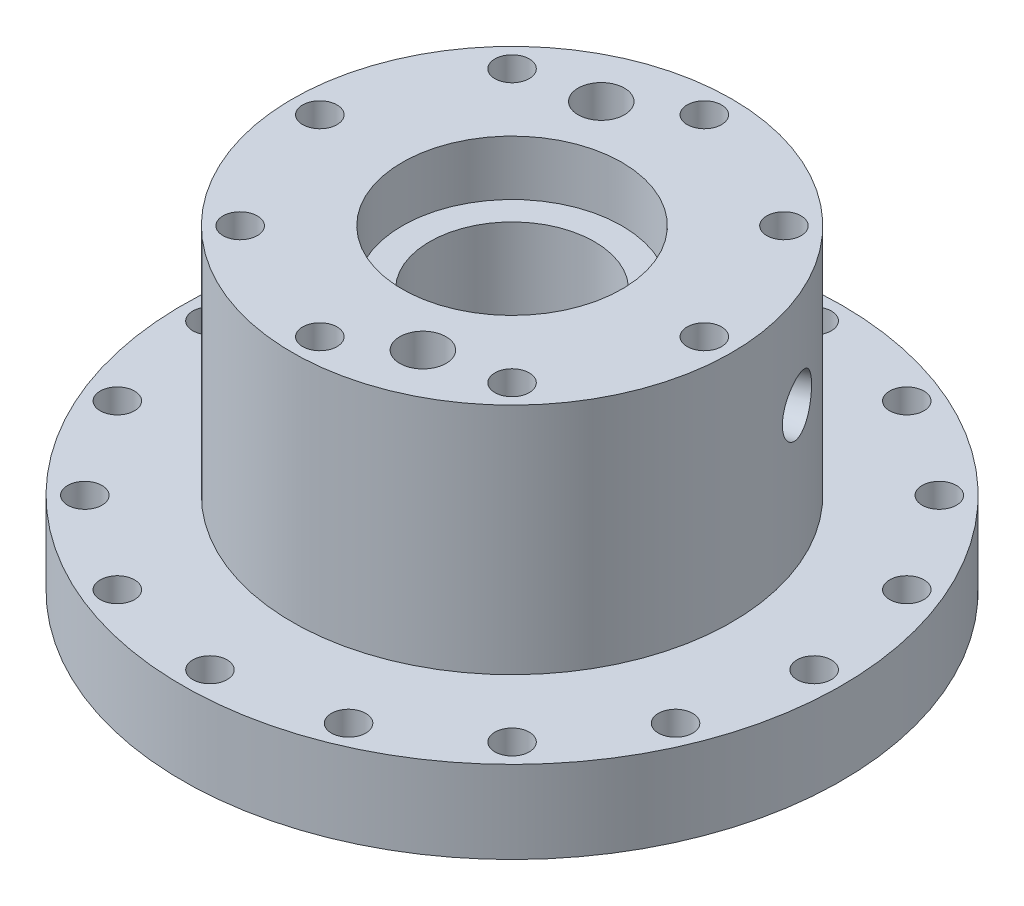
SolidWorks part; units mm, degrees
material "6061-T4 (SS)"
ref_plane "Front Plane" through (0, 0, 0) normal (0, 0, 1) x (1, 0, 0)
ref_plane "Top Plane" through (0, 0, 0) normal (0, 1, 0) x (1, 0, 0)
ref_plane "Right Plane" through (0, 0, 0) normal (1, 0, 0) x (0, 0, -1)
sketch "Sketch1" plane through (0, 0, 0) normal (0, 0, 1) x (1, 0, 0)
  line L0 (-76.2, 19.05) -> (-76.2, 0)
  line L1 (-76.2, 0) -> (-42.8625, 0)
  line L3 (-50.8, 19.05) -> (-76.2, 19.05)
  line L9 (-42.8625, 0) -> (-25.4, 15.875)
  line L10 (-25.4, 15.875) -> (-19.05, 15.875)
  line L11 (-19.05, 15.875) -> (-19.05, 60.325)
  line L12 (-19.05, 60.325) -> (-25.4, 60.325)
  line L13 (-25.4, 60.325) -> (-25.4, 73.025)
  line L14 (-25.4, 73.025) -> (-50.8, 73.025)
  line L15 (-50.8, 73.025) -> (-50.8, 19.05)
  line L16 (0, 0) -> (0, 51.8362) construction
  dimension "D1" = 76.2
  dimension "D2" = 19.05
  dimension "D3" = 33.3375
  dimension "D4" = 19.05
  dimension "D5" = 6.35
  dimension "D6" = 15.875
  dimension "D7" = 44.45
  dimension "D8" = 12.7
  dimension "D9" = 6.35
  dimension "D10" = 25.4
revolve "Revolve1" add sketch "Sketch1" angle 360 about L16
hole_wizard "5/16 (0.3125) Diameter Hole1" positions "Sketch4" profile "Sketch5" hole size "5/16" standard "ANSI Inch"
sketch "Sketch4" plane through (0, 19.05, 0) normal (0, 1, 0) x (1, 0, 0)
  point P0 (-69.85, 0)
  dimension "D1" = 69.85
sketch "Sketch5" plane through (-69.85, 19.05, 0) normal (1, 0, 0) x (0, 0, 1)
  line L0 (0, 0) -> (0, 40.4847)
  line L1 (0, 40.4847) -> (3.9687, 38.1)
  line L2 (3.9687, 38.1) -> (3.9687, 0)
  line L5 (3.9687, 0) -> (0, 0)
  line L10 (0, 40.4847) -> (-3.9688, 38.1) construction
  line L11 (0, -6.35) -> (0, 107.95) construction
  dimension "Hole Dia." = 7.9375
  dimension "Hole Depth" = 38.1
  dimension "Drill Angle" = 118
ref_axis "Axis1" through (0, 0.635, 0) along (0, -1, 0)
pattern_circular "CirPattern1" count 16 over 360 about axis through (0, 0.635, 0) along (0, -1, 0) of "5/16 (0.3125) Diameter Hole1"
hole_wizard "5/16 (0.3125) Diameter Hole2" positions "Sketch6" profile "Sketch7" hole size "5/16" standard "ANSI Inch"
sketch "Sketch6" plane through (0, 73.025, 0) normal (0, 1, 0) x (1, 0, 0)
  point P0 (44.45, 0)
  dimension "D1" = 44.45
sketch "Sketch7" plane through (44.45, 73.025, 0) normal (1, 0, 0) x (0, 0, 1)
  line L0 (0, 0) -> (0, 27.7847)
  line L1 (0, 27.7847) -> (3.9687, 25.4)
  line L2 (3.9687, 25.4) -> (3.9687, 0)
  line L5 (3.9687, 0) -> (0, 0)
  line L10 (0, 27.7847) -> (-3.9688, 25.4) construction
  line L11 (0, -6.35) -> (0, 107.95) construction
  dimension "Hole Dia." = 7.9375
  dimension "Hole Depth" = 25.4
  dimension "Drill Angle" = 118
pattern_circular "CirPattern2" count 8 over 360 about axis through (0, 0, 0) along (0, -1, 0) of "5/16 (0.3125) Diameter Hole2"
ref_plane "Plane1" through (46.9331, 0, -19.4403) normal (0.9239, 0, -0.3827) x (0, -1, 0)
hole_wizard "1/4 NPT Tapped Hole1" positions "Sketch8" profile "Sketch9" size "1/4" standard "ANSI Inch"
sketch "Sketch8" plane through (46.9331, 0, -19.4403) normal (0.9239, 0, -0.3827) x (0, -1, 0)
  line L0 (-73.025, 50.8) -> (-73.025, -50.8) construction
  point P0 (-50.8, 0)
  point P3 (-62.9792, 0)
  point P5 (-66.9227, 0)
  point P6 (-78.9221, 0)
  dimension "D1" = 22.225
sketch "Sketch9" plane through (46.9331, 50.8, -19.4403) normal (0, 1, 0) x (-0.3827, 0, -0.9239)
  line L0 (0, 0) -> (0, 41.4423)
  line L1 (5.5626, 38.1) -> (0, 41.4423)
  line L2 (-5.5626, 38.1) -> (0, 41.4423) construction
  line L3 (5.5626, 38.1) -> (5.5626, 9.906)
  line L4 (5.5626, 9.906) -> (5.9437, 9.906)
  line L5 (5.9437, 9.906) -> (6.2403, 0)
  line L6 (-5.9437, 9.906) -> (-6.2403, 0) construction
  line L7 (6.2403, 0) -> (0, 0)
  line L8 (0, -6.35) -> (0, 107.95) construction
  line L11 (-5.5626, 9.906) -> (-5.9437, 9.906) construction
  dimension "Tap Drill Dia." = 11.1252
  dimension "Tap Drill Depth" = 38.1
  dimension "Thread Dia." = 12.4806
  dimension "Thread Angle" = 3.43
  dimension "Thread Depth" = 9.906
  dimension "Drill Angle" = 118
cosmetic thread "Hole Thread1" parameters "D1"=9.906, "D2"=13.7086
hole_wizard "Tap Drill for 1/2-13 Tap1" positions "Sketch12" profile "Sketch13" hole size "1/2-13" standard "ANSI Inch"
sketch "Sketch12" plane through (0, 73.025, 0) normal (0, 1, 0) x (1, 0, 0)
  line L0 (0, 33.8578) -> (0, 0) construction
  line L1 (0, 0) -> (-14.5802, 35.1998) construction
  point P0 (-14.5802, 35.1998)
  dimension "D1" = 22.5
  dimension "D2" = 38.1
sketch "Sketch13" plane through (-14.5802, 73.025, -35.1998) normal (1, 0, 0) x (0, 0, 1)
  line L0 (0, 0) -> (0, 66.7195)
  line L1 (0, 66.7195) -> (5.3581, 63.5)
  line L2 (5.3581, 63.5) -> (5.3581, 0)
  line L5 (5.3581, 0) -> (0, 0)
  line L10 (0, 66.7195) -> (-5.3581, 63.5) construction
  line L11 (0, -6.35) -> (0, 107.95) construction
  dimension "Hole Dia." = 10.7163
  dimension "Hole Depth" = 63.5
  dimension "Drill Angle" = 118
pattern_circular "CirPattern3" count 2 over 360 about axis through (0, 0, 0) along (0, -1, 0) of "Tap Drill for 1/2-13 Tap1"
